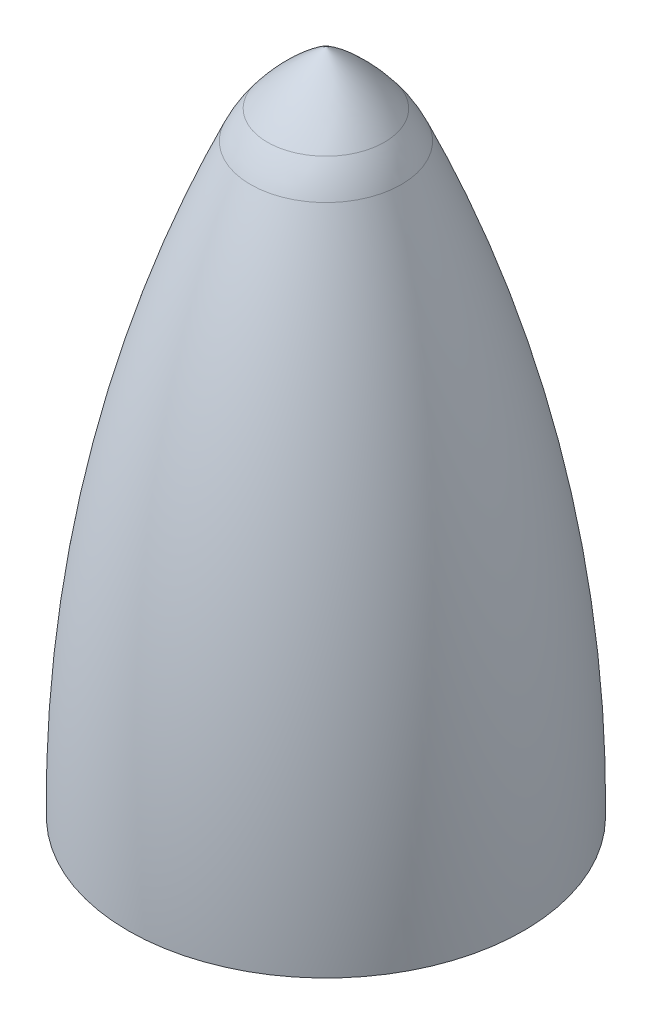
SolidWorks part; units mm, degrees
ref_plane "Front Plane" through (0, 0, 0) normal (0, 0, 1) x (1, 0, 0)
ref_plane "Top Plane" through (0, 0, 0) normal (0, 1, 0) x (1, 0, 0)
ref_plane "Right Plane" through (0, 0, 0) normal (1, 0, 0) x (0, 0, -1)
sketch "Sketch1" plane through (0, 0, 0) normal (0, 1, 0) x (1, 0, 0)
  circle A0 centre (0, 0) radius 38.85
  dimension "D1" = 77.7
extrude "Boss-Extrude1" add sketch "Sketch1" along normal blind 5
sketch "Sketch4" plane through (0, 0, 0) normal (0, 0, 1) x (1, 0, 0)
  line L0 (0, 5) -> (0, 7)
  line L2 (-42.35, 5) -> (0, 5)
  line L4 (0, 135) -> (0, 150)
  line L5 (38.85, 5) -> (-38.85, 5) construction
  line L6 (0, 7) -> (-39.35, 7)
  line L7 (0, 135) -> (-12, 135)
  arc A0 (-15, 135) -> (-42.35, 5) centre (257.6121, 9.7696) ccw
  arc A1 (-15, 135) -> (0, 150) centre (27.0507, 107.9493) cw
  arc A2 (-39.35, 7) -> (-12, 135) centre (260.6367, 9.8232) cw
  dimension "D4" = 300
  dimension "D7" = 50
  dimension "D1" = 15
  dimension "D2" = 5
  dimension "D3" = 42.35
  dimension "D5" = 130
  dimension "D6" = 15
  dimension "D8" = 3
  dimension "D9" = 3
  dimension "D10" = 2
  dimension "D11" = 42.35
revolve "Revolve1" add sketch "Sketch4" angle 360 about L0
fillet "Fillet1" radius 30 1 edges at (0, 135, -15)
sketch "Sketch5" plane through (0, 0, 0) normal (0, 1, 0) x (1, 0, 0)
  circle A0 centre (0, 0) radius 42.4
  dimension "D1" = 84.8
extrude "Cut-Extrude1" cut sketch "Sketch5" along normal blind 7
sketch "Sketch6" plane through (0, 135, 0) normal (0, -1, 0) x (1, 0, 0)
  circle A0 centre (0, 0) radius 4.5
  dimension "D1" = 9
extrude "Boss-Extrude2" add sketch "Sketch6" along normal blind 10
thread "Thread1" pitch 2.5 method cut profile "Thread Profile1" start angle 0, offset 0, length 0, pitch 2.5, diameter 9
ref_plane "Plane1" through (4.5, 125, 0) normal (0, 0, 1) x (1, 0, 0)
sketch "Thread Profile1" plane through (4.5, 125, 0) normal (0, 0, 1) x (1, 0, 0)
  line L0 (0, 0) -> (0, 2.5) construction
  line L11 (0, 0) -> (0, 2.1875)
  line L12 (0, 2.1875) -> (-1.3532, 1.4062)
  line L13 (-1.3532, 1.4062) -> (-1.3532, 0.7812)
  line L15 (-1.3532, 0.7812) -> (0, 0)
  line L17 (-1.3532, 1.0937) -> (0, 1.0937) construction
  point P2 (0, 0)
  dimension "Pitch" = 2.5
  dimension "Profile_Angle" = 60
  dimension "Profile_Land" = 0.625
  dimension "Profile_Height" = 1.3532
sketch "Sketch9" plane through (0, 125, 0) normal (0, -1, 0) x (1, 0, 0)
  circle A1 centre (0, 0) radius 4.5
  circle A2 centre (0, 0) radius 4.5
  dimension "D1" = 0
extrude "Cut-Extrude2" cut sketch "Sketch9" against normal blind 1
